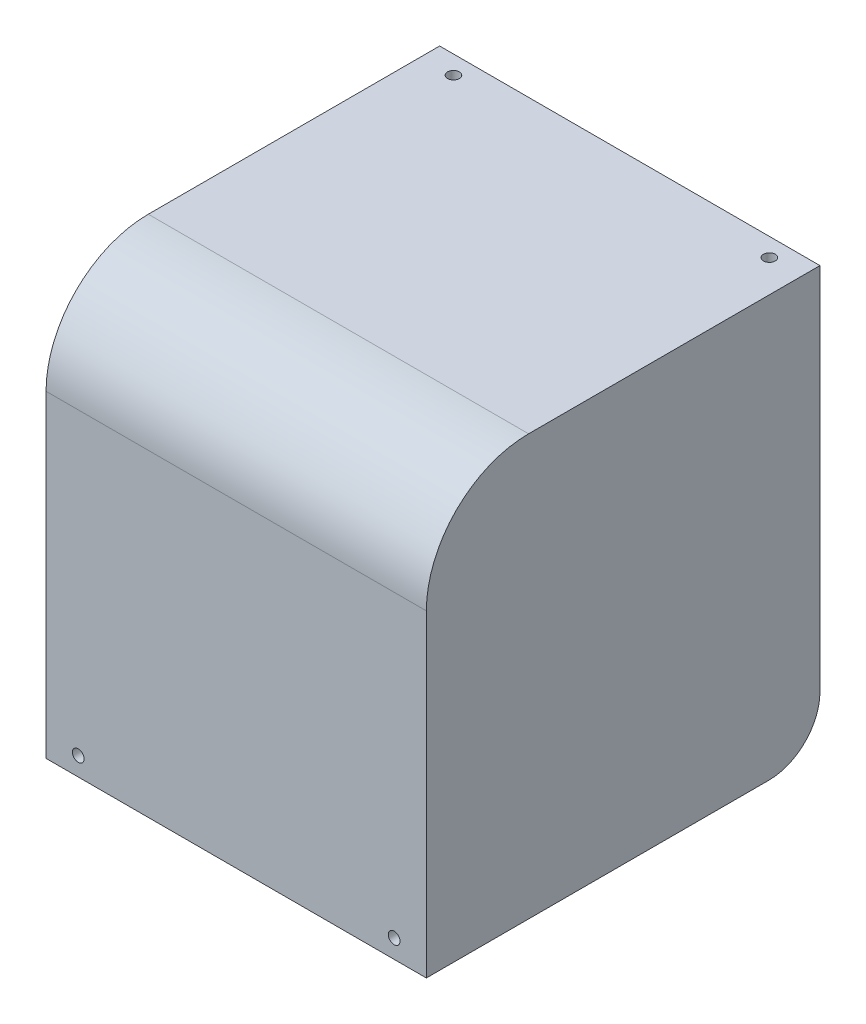
SolidWorks part; units mm, degrees
ref_plane "Front Plane" through (0, 0, 0) normal (0, 0, 1) x (1, 0, 0)
ref_plane "Top Plane" through (0, 0, 0) normal (0, 1, 0) x (1, 0, 0)
ref_plane "Right Plane" through (0, 0, 0) normal (1, 0, 0) x (0, 0, -1)
sketch "Sketch1" plane through (0, 0, 0) normal (1, 0, 0) x (0, 0, -1)
  line L0 (0, 0) -> (0, 82.2)
  line L1 (0, 82.2) -> (77, 82.2)
  line L2 (77, 82.2) -> (77, 80.2)
  line L3 (77, 80.2) -> (2, 80.2)
  line L4 (2, 80.2) -> (2, 0)
  line L5 (2, 0) -> (0, 0)
  dimension "D1" = 80.2
  dimension "D2" = 75
  dimension "D3" = 2
  dimension "D4" = 2
extrude "Boss-Extrude1" add sketch "Sketch1" along normal mid plane 74.4
sketch "Sketch2" plane through (0, 0, 0) normal (0, 0, 1) x (1, 0, 0)
  line L0 (-37.2, 3.64) -> (37.2, 3.64) construction
  line L1 (-37.2, 82.2) -> (-37.2, 0) construction
  line L2 (37.2, 82.2) -> (37.2, 0) construction
  line L3 (0, 3.64) -> (0, 0) construction
  line L4 (37.2, 0) -> (-37.2, 0) construction
  circle A0 centre (-30.9, 3.64) radius 1.15
  circle A1 centre (30.9, 3.64) radius 1.15
  dimension "D2" = 2.3
  dimension "D1" = 61.8
  dimension "D3" = 3.64
extrude "Cut-Extrude1" cut sketch "Sketch2" against normal blind 70
fillet "Fillet1" radius 20 2 edges at (0, 82.2, 0) (0, 80.2, -2)
sketch "Sketch3" plane through (-37.2, 0, 0) normal (-1, 0, 0) x (0, 0, 1)
  line L0 (-77, 80.2) -> (-77, 0)
  line L1 (-77, 0) -> (-2, 0)
  line L2 (-2, 0) -> (-2, 60.2) construction
  line L3 (-22, 80.2) -> (-77, 80.2) construction
  line L4 (-2, 0) -> (-2, 60.2)
  line L5 (-22, 80.2) -> (-77, 80.2)
  arc A0 (-2, 60.2) -> (-22, 80.2) centre (-22, 60.2) ccw construction
  arc A1 (-2, 60.2) -> (-22, 80.2) centre (-22, 60.2) ccw
extrude "Boss-Extrude2" add sketch "Sketch3" against normal blind 2
mirror "Mirror1" about plane through (0, 0, 0) normal (1, 0, 0) of "Boss-Extrude2"
fillet "Fillet2" radius 10 2 edges at (-36.2, 0, -77) (36.2, 0, -77)
sketch "Sketch4" plane through (0, 82.2, 0) normal (0, 1, 0) x (1, 0, 0)
  line L0 (-37.2, 73.402) -> (37.2, 73.402) construction
  line L1 (0, 73.402) -> (0, 77) construction
  line L2 (37.2, 77) -> (37.2, 20) construction
  line L3 (-37.2, 77) -> (-37.2, 20) construction
  line L4 (37.2, 77) -> (-37.2, 77) construction
  circle A0 centre (-30.9, 73.402) radius 1.15
  circle A1 centre (30.9, 73.402) radius 1.15
  dimension "D1" = 2.3
  dimension "D2" = 61.8
  dimension "D3" = 3.598
extrude "Cut-Extrude2" cut sketch "Sketch4" against normal blind 10
